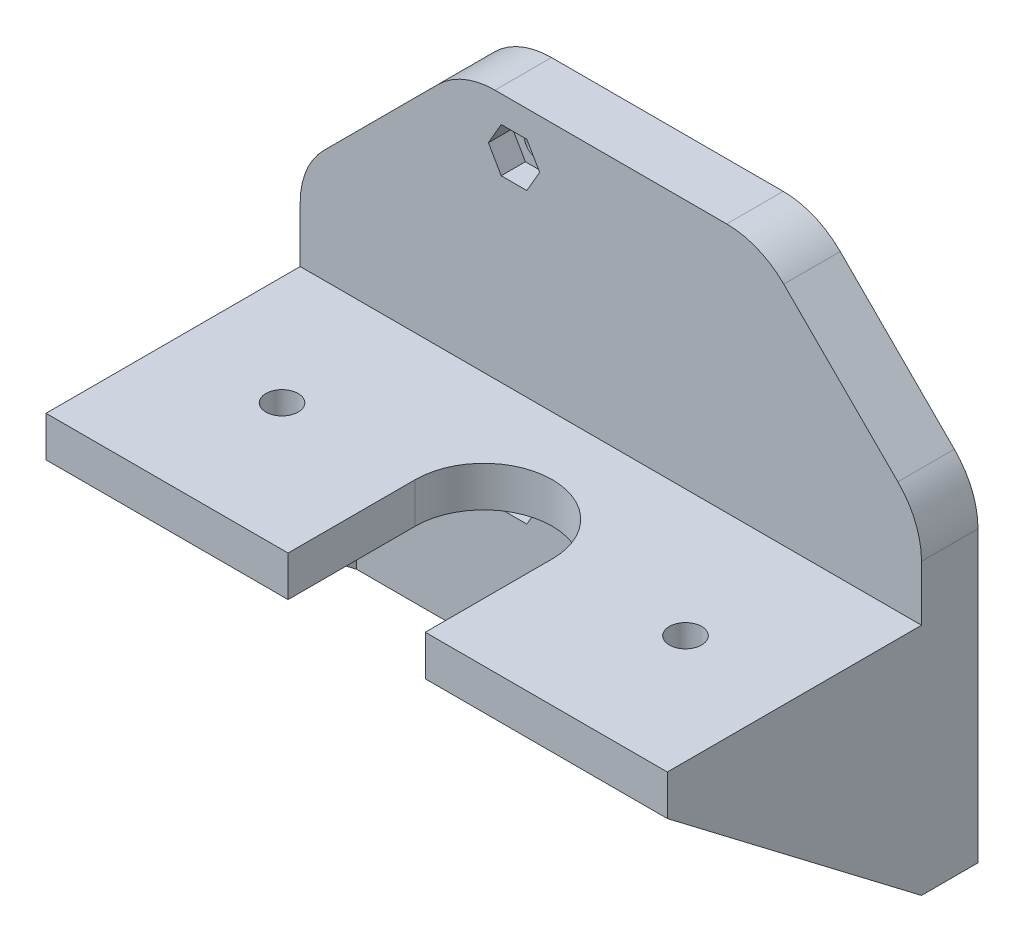
SolidWorks part; units mm, degrees
ref_plane "Front Plane" through (0, 0, 0) normal (0, 0, 1) x (1, 0, 0)
ref_plane "Top Plane" through (0, 0, 0) normal (0, 1, 0) x (1, 0, 0)
ref_plane "Right Plane" through (0, 0, 0) normal (1, 0, 0) x (0, 0, -1)
sketch "Sketch1" plane through (0, 0, 0) normal (0, 0, 1) x (1, 0, 0)
  line L1 (-50.5, 41.85) -> (26.5, 41.85)
  line L2 (-50.5, 41.85) -> (-50.5, -18.15)
  line L3 (-50.5, -18.15) -> (26.5, -18.15)
  line L4 (26.5, 41.85) -> (26.5, -18.15)
  circle A0 centre (-24, 35.8) radius 1.75
  circle A1 centre (-24, 0) radius 1.75
  circle A2 centre (0, 0) radius 1.75
  dimension "D1" = 35.8
  dimension "D2" = 3.5
  dimension "D3" = 24
  dimension "D4" = 77
  dimension "D5" = 26.5
  dimension "D6" = 60
  dimension "D7" = 18.15
extrude "Boss-Extrude1" add sketch "Sketch1" along normal blind 7
sketch "Sketch2" plane through (0, 0, 7) normal (0, 0, 1) x (1, 0, 0)
  line L0 (-50.5, 41.85) -> (-50.5, -18.15) construction
  line L1 (-50.5, 10.85) -> (26.5, 10.85)
  line L2 (-50.5, 10.85) -> (-50.5, 5.85)
  line L3 (-50.5, 5.85) -> (26.5, 5.85)
  line L4 (26.5, 10.85) -> (26.5, 5.85)
  line L5 (26.5, -18.15) -> (26.5, 41.85) construction
  line L6 (-50.5, -18.15) -> (26.5, -18.15) construction
  dimension "D1" = 5
  dimension "D2" = 24
extrude "Boss-Extrude2" add sketch "Sketch2" along normal blind 31.5
sketch "Sketch3" plane through (0, 10.85, 0) normal (0, 1, 0) x (1, 0, 0)
  line L0 (-12, -38.5) -> (-12, -7) construction
  line L1 (26.5, -38.5) -> (-50.5, -38.5) construction
  line L2 (26.5, -7) -> (-50.5, -7) construction
  line L3 (-20.5, -22.75) -> (-20.5, -38.5)
  line L4 (-3.5, -22.75) -> (-3.5, -38.5)
  line L5 (-3.5, -38.5) -> (-20.5, -38.5)
  arc A0 (-3.5, -22.75) -> (-20.5, -22.75) centre (-12, -22.75) ccw
  dimension "D1" = 17
extrude "Cut-Extrude1" cut sketch "Sketch3" against normal blind 20
sketch "Sketch4" plane through (0, 10.85, 0) normal (0, 1, 0) x (1, 0, 0)
  line L0 (26.5, -22.75) -> (-50.5, -22.75) construction
  line L1 (26.5, -38.5) -> (26.5, -7) construction
  line L2 (-50.5, -38.5) -> (-50.5, -7) construction
  circle A0 centre (13, -22.75) radius 2
  circle A1 centre (-37, -22.75) radius 2
  dimension "D1" = 4
  dimension "D2" = 50
  dimension "D3" = 13.5
extrude "Cut-Extrude2" cut sketch "Sketch4" against normal blind 20
sketch "Sketch5" plane through (26.5, 0, 0) normal (1, 0, 0) x (0, 0, -1)
  line L0 (-38.5, 5.85) -> (-7, -18.15)
rib "Rib2" sketch "Sketch5" sketch "Sketch5" thickness 7 extrusion direction parallel to sketch draft on no parameters "D1"=7
ref_plane "Plane1" through (-12, 0, 0) normal (1, 0, 0) x (0, 0, -1)
mirror "Mirror1" about plane through (-12, 0, 0) normal (1, 0, 0) of "Rib2"
chamfer "Chamfer1" distance 20 angle 45 2 edges at (-50.5, 41.85, 3.5) (26.5, 41.85, 3.5)
fillet "Fillet1" radius 10 4 edges at (-50.5, 21.85, 3.5) (-30.5, 41.85, 3.5) (26.5, 21.85, 3.5) (6.5, 41.85, 3.5)
sketch "Sketch6" plane through (0, 0, 7) normal (0, 0, 1) x (1, 0, 0)
  line L1 (-22.4123, 33.05) -> (-20.8246, 35.8)
  line L2 (-20.8246, 35.8) -> (-22.4123, 38.55)
  line L3 (-22.4123, 38.55) -> (-25.5877, 38.55)
  line L4 (-25.5877, 38.55) -> (-27.1754, 35.8)
  line L5 (-27.1754, 35.8) -> (-25.5877, 33.05)
  line L6 (-25.5877, 33.05) -> (-22.4123, 33.05)
  line L7 (-22.4123, -2.75) -> (-20.8246, 0)
  line L8 (-20.8246, 0) -> (-22.4123, 2.75)
  line L9 (-22.4123, 2.75) -> (-25.5877, 2.75)
  line L10 (-25.5877, 2.75) -> (-27.1754, 0)
  line L11 (-27.1754, 0) -> (-25.5877, -2.75)
  line L12 (-25.5877, -2.75) -> (-22.4123, -2.75)
  line L13 (1.5877, -2.75) -> (3.1754, 0)
  line L14 (3.1754, 0) -> (1.5877, 2.75)
  line L15 (1.5877, 2.75) -> (-1.5877, 2.75)
  line L16 (-1.5877, 2.75) -> (-3.1754, 0)
  line L17 (-3.1754, 0) -> (-1.5877, -2.75)
  line L18 (-1.5877, -2.75) -> (1.5877, -2.75)
  circle A0 centre (-24, 35.8) radius 2.75 construction
  circle A1 centre (-24, 0) radius 2.75 construction
  circle A2 centre (0, 0) radius 2.75 construction
  dimension "D1" = 5.5
extrude "Cut-Extrude3" cut sketch "Sketch6" against normal blind 3
equation "\"D5@Sketch1\"=(\"D4@Sketch1\"-\"D3@Sketch1\")/2"
equation "\"D7@Sketch1\"=3*(\"D6@Sketch1\"-\"D1@Sketch1\")/4"
equation "\"D3@Sketch4\"=(77-50)/2"
